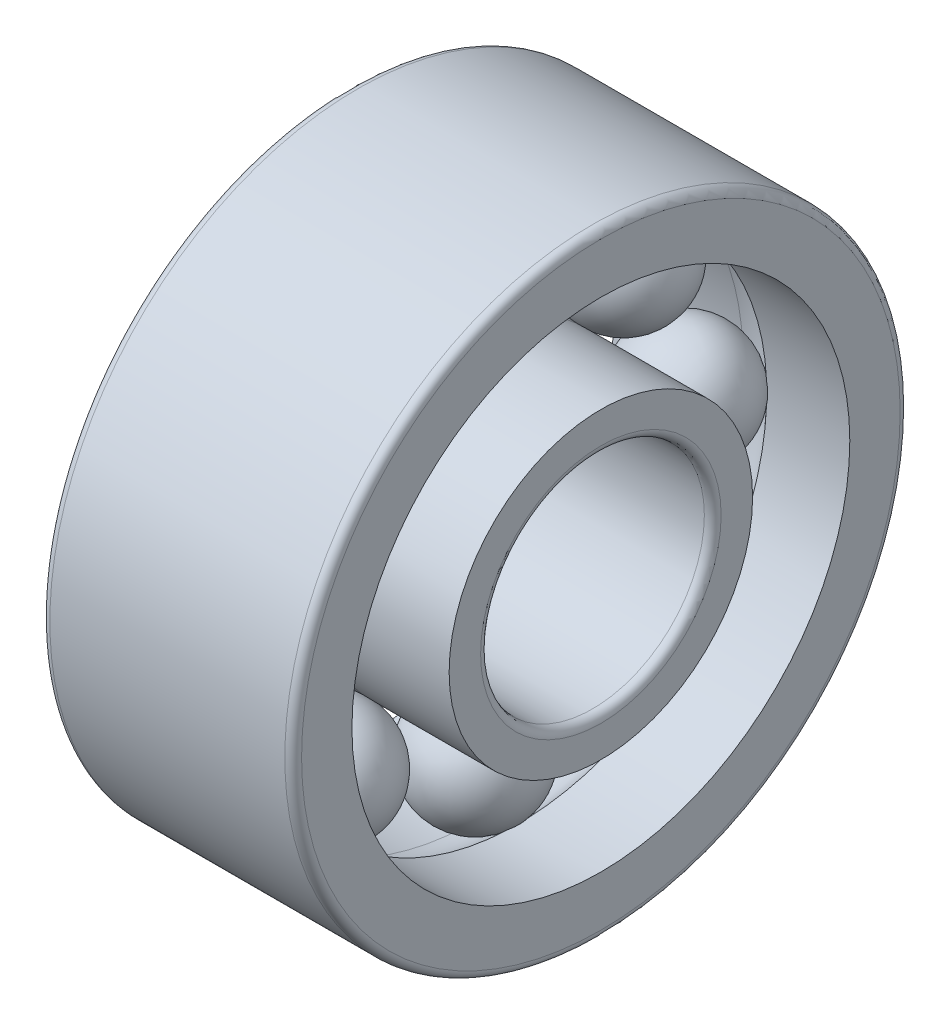
SolidWorks part; units mm, degrees
material "AISI 1020 Acero laminado en frío"
ref_plane "Plane1" through (0, 0, 0) normal (0, 0, 1) x (1, 0, 0)
ref_plane "Plane2" through (0, 0, 0) normal (0, 1, 0) x (1, 0, 0)
ref_plane "Plane3" through (0, 0, 0) normal (1, 0, 0) x (0, 0, -1)
sketch "Clipboard" plane through (0, 0, 0) normal (0, 0, 1) x (1, 0, 0)
  line L0 (-10, 0) -> (10, 0) construction
  line L1 (0, 0) -> (22.1431, -3.112)
  line L2 (0, 0) -> (7.427, 1.0438)
  line L3 (0, 0) -> (22.1431, -3.112)
  line L4 (0, 0) -> (-22.3573, -0.3902)
  dimension "BallCLRad" = 7.5
sketch "CagSpiSke" plane through (0, 0, 0) normal (0, 0, 1) x (1, 0, 0)
  line L0 (0.525, 7.15) -> (0.525, 7.85)
  line L1 (0.525, 7.85) -> (-0.525, 7.85)
  line L2 (-0.525, 7.85) -> (-0.525, 7.15)
  line L3 (-0.525, 7.15) -> (0.525, 7.15)
  line L4 (-20.6375, 0) -> (20.6375, 0) construction
  line L5 (0, 0) -> (0, 23.7692) construction
  dimension "OD" = 15.7
  dimension "ID" = 14.3
revolve "CageSpine" add sketch "CagSpiSke" angle 0.001 about L4
ref_axis "Axis1" through (-50, 0, 0) along (1, 0, 0)
sketch "CagBalSke" plane through (0, 0, 0) normal (0, 0, 1) x (1, 0, 0)
  line L0 (-2.31, 7.5) -> (2.31, 7.5)
  line L1 (-1.905, 7.5) -> (1.905, 7.5) construction
  line L2 (-10, 0) -> (10, 0) construction
  line L3 (0, 0) -> (0, 24) construction
  arc A0 (2.31, 7.5) -> (-2.31, 7.5) centre (0, 7.5) cw
  dimension "BallCLRad" = 7.5
revolve "CageBall" [suppressed] add sketch "CagBalSke" angle 360 about L1 reverse direction yes
pattern_circular "CageBalls" [suppressed] count 8 every 45 about axis through (-50, 0, 0) along (1, 0, 0)
sketch "CagTrmODSke" plane through (0, 0, 0) normal (0, 0, 1) x (1, 0, 0)
  line L0 (2.311, 7.85) -> (2.311, 9.811)
  line L1 (2.311, 9.811) -> (-2.311, 9.811)
  line L2 (-2.311, 9.811) -> (-2.311, 7.85)
  line L3 (-2.311, 7.85) -> (2.311, 7.85)
  line L4 (-20.6375, 0) -> (20.6375, 0) construction
  line L5 (0, 0) -> (0, 25) construction
  dimension "Width" = 4.622
  dimension "ID" = 15.7
  dimension "OD" = 19.622
revolve "CageTrimOD" [suppressed] cut sketch "CagTrmODSke" angle 360 about L4 reverse direction yes
sketch "CagTrmIDSke" plane through (0, 0, 0) normal (0, 0, 1) x (1, 0, 0)
  line L0 (2.311, 5.191) -> (2.311, 7.15)
  line L1 (2.311, 7.15) -> (-2.311, 7.15)
  line L2 (-2.311, 7.15) -> (-2.311, 5.191)
  line L3 (-2.311, 5.191) -> (2.311, 5.191)
  line L4 (-20.6375, 0) -> (20.6375, 0) construction
  line L5 (0, 0) -> (0, 25) construction
  dimension "Width" = 4.622
  dimension "ID" = 10.382
  dimension "OD" = 14.3
revolve "CageTrimID" [suppressed] cut sketch "CagTrmIDSke" angle 360 about L4 reverse direction yes
sketch "BalSimSke" plane through (0, 0, 0) normal (0, 0, 1) x (1, 0, 0)
  line L0 (-10, 0) -> (10, 0) construction
  line L1 (-10, 7.5) -> (10, 7.5) construction
  line L2 (0, 0) -> (0, 23) construction
  circle A0 centre (0, 7.5) radius 2.1
  dimension "BallCLRad" = 7.5
  dimension "Ball_diameter" = 4.2
revolve "BallsSimplified" [suppressed] add sketch "BalSimSke" angle 360 about L0
sketch "BalDetSke" plane through (0, 0, 0) normal (0, 0, 1) x (1, 0, 0)
  line L0 (-2.1, 7.5) -> (2.1, 7.5)
  line L1 (-1.905, 7.5) -> (1.905, 7.5) construction
  line L2 (0, 0) -> (0, 25) construction
  arc A0 (2.1, 7.5) -> (-2.1, 7.5) centre (0, 7.5) cw
  dimension "BallCLRad" = 7.5
  dimension "Ball_diameter" = 4.2
revolve "BallDetailed" add sketch "BalDetSke" angle 360 about L1 reverse direction yes
sketch "InnRacSke" plane through (0, 0, 0) normal (0, 0, 1) x (1, 0, 0)
  line L0 (-1.5315, 6.1) -> (-4.5, 6.1)
  line L1 (-4.5, 6.1) -> (-4.5, 4.3)
  line L2 (-4.2, 4) -> (4.2, 4)
  line L3 (4.5, 4.3) -> (4.5, 5.425)
  line L4 (0, 5.425) -> (4.5, 5.425)
  line L5 (-20.6375, 0) -> (20.6375, 0) construction
  line L6 (0, 0) -> (0, 30) construction
  arc A0 (-4.5, 4.3) -> (-4.2, 4) centre (-4.2, 4.3) ccw
  arc A1 (4.2, 4) -> (4.5, 4.3) centre (4.2, 4.3) ccw
  arc A2 (0, 5.425) -> (-1.5315, 6.1) centre (0, 7.5) cw
  dimension "BallCLRad" = 7.5
  dimension "Fillet_radius" = 0.3
  dimension "Ball_diameter" = 4.15
  dimension "ID" = 8
  dimension "OD" = 12.2
  dimension "Width" = 9
revolve "InnerRace" add sketch "InnRacSke" angle 360 about L5 reverse direction yes
sketch "OutRacSke" plane through (0, 0, 0) normal (0, 0, 1) x (1, 0, 0)
  line L0 (0, 9.575) -> (-4.5, 9.575)
  line L1 (-4.5, 9.575) -> (-4.5, 10.7)
  line L2 (-4.2, 11) -> (4.2, 11)
  line L3 (4.5, 10.7) -> (4.5, 8.9)
  line L4 (4.5, 8.9) -> (1.5315, 8.9)
  line L5 (-20.6375, 0) -> (20.6375, 0) construction
  line L6 (0, 0) -> (0, 30) construction
  arc A0 (-4.5, 10.7) -> (-4.2, 11) centre (-4.2, 10.7) cw
  arc A1 (4.2, 11) -> (4.5, 10.7) centre (4.2, 10.7) cw
  arc A2 (1.5315, 8.9) -> (0, 9.575) centre (0, 7.5) ccw
  dimension "BallCLRad" = 7.5
  dimension "Fillet_radius" = 0.3
  dimension "Ball_diameter" = 4.15
  dimension "Width" = 9
revolve "OuterRace" add sketch "OutRacSke" angle 360 about L5 reverse direction yes
pattern_circular "BallsDetailed" count 8 every 45 about axis through (-50, 0, 0) along (1, 0, 0) of "BallDetailed"
equation "\"BallCLRad@Clipboard\" = ( \"OD@OutRacSke\" + \"ID@InnRacSke\" ) / 4"
equation "\"BallCLRad@BalSimSke\" = \"BallCLRad@Clipboard\""
equation "\"BallCLRad@BalDetSke\" = \"BallCLRad@Clipboard\""
equation "\"BallCLRad@InnRacSke\" = \"BallCLRad@Clipboard\""
equation "\"BallCLRad@OutRacSke\" = \"BallCLRad@Clipboard\""
equation "\"Ball_diameter@InnRacSke\" = \"Ball_diameter@BalDetSke\" - 0.05"
equation "\"Ball_diameter@OutRacSke\" = \"Ball_diameter@BalDetSke\" - 0.05"
equation "\"Ball_diameter@BalSimSke\" = \"Ball_diameter@BalDetSke\""
equation "\"Width@OutRacSke\" = \"Width@InnRacSke\""
equation "\"Fillet_radius@OutRacSke\" = \"Fillet_radius@InnRacSke\""
equation "\"Max_count@Clipboard\" = int( 3.14159265 / atn(( \"Ball_diameter@BalDetSke\" / 2) / sqr( \"BallCLRad@Clipboard\"  *  \"BallCLRad@Clipboard\" - ( \"Ball_diameter@BalDetSke\" / 2) *  ( \"Ball_diameter@BalDetSke\" / 2))))"
equation "\"Max_count@Clipboard\" = ((sgn( \"Max_count@Clipboard\" - \"Count@Clipboard\" )-1)*( \"Max_count@Clipboard\" - \"Count@Clipboard\" ))/-2+ \"Count@Clipboard\""
equation "\"Count@BallsDetailed\" = int( \"Show_count@Clipboard\" ) "
equation "\"Count@BallsDetailed\" = ((sgn( \"Count@BallsDetailed\" - \"Max_count@Clipboard\" )-1)*( \"Count@BallsDetailed\" - \"Max_count@Clipboard\" ))/-2+ \"Max_count@Clipboard\""
equation "\"Count@BallsDetailed\" = ((sgn( \"Count@BallsDetailed\" - \"Min_count@Clipboard\" )+1)*( \"Count@BallsDetailed\" - \"Min_count@Clipboard\"))/2 +\"Min_count@Clipboard\""
equation "\"Angle@BallsDetailed\" = 360.0 / \"Max_count@Clipboard\""
equation "\"BallCLRad@CagBalSke\" = \"BallCLRad@Clipboard\""
equation "\"Count@CageBalls\" = \"Count@BallsDetailed\""
equation "\"Angle@CageBalls\" = \"Angle@BallsDetailed\""
equation "\"Angle@CageSpine\" =  \"Angle@CageBalls\" * ( \"Count@CageBalls\" -1 + int( \"Count@CageBalls\" / \"Max_count@Clipboard\" ) )  + 0.001 -  int( \"Count@CageBalls\" / \"Max_count@Clipboard\" ) * 0.001"
equation "\"Angle@CageSpine\" =  \"Angle@CageSpine\" * int( \"Min_count@Clipboard\" / 2) + int(1 / \"Min_count@Clipboard\")  * 0.001"
equation "\"CageWallOD@CagBalSke\" =  \"Ball_diameter@BalDetSke\" * 1.1"
equation "\"Thickness@CagSpiSke\" =  \"Ball_diameter@BalDetSke\" * 0.25"
equation "\"OD@CagTrmODSke\" = \"BallCLRad@Clipboard\" * 2 + \"CageWallOD@CagBalSke\" + 0.002"
equation "\"ID@CagTrmODSke\" = \"BallCLRad@Clipboard\" * 2 + \"Ball_diameter@BalDetSke\" / 6"
equation "\"OD@CagTrmIDSke\" = \"BallCLRad@Clipboard\" * 2 - \"Ball_diameter@BalDetSke\" / 6"
equation "\"ID@CagTrmIDSke\" = \"BallCLRad@Clipboard\" * 2 - \"CageWallOD@CagBalSke\" + 0.002"
equation "\"OD@CagSpiSke\" = \"ID@CagTrmODSke\""
equation "\"ID@CagSpiSke\" = \"OD@CagTrmIDSke\""
equation "\"Width@CagTrmODSke\" = \"CageWallOD@CagBalSke\" + 0.002"
equation "\"Width@CagTrmIDSke\" = \"CageWallOD@CagBalSke\" + 0.002"
